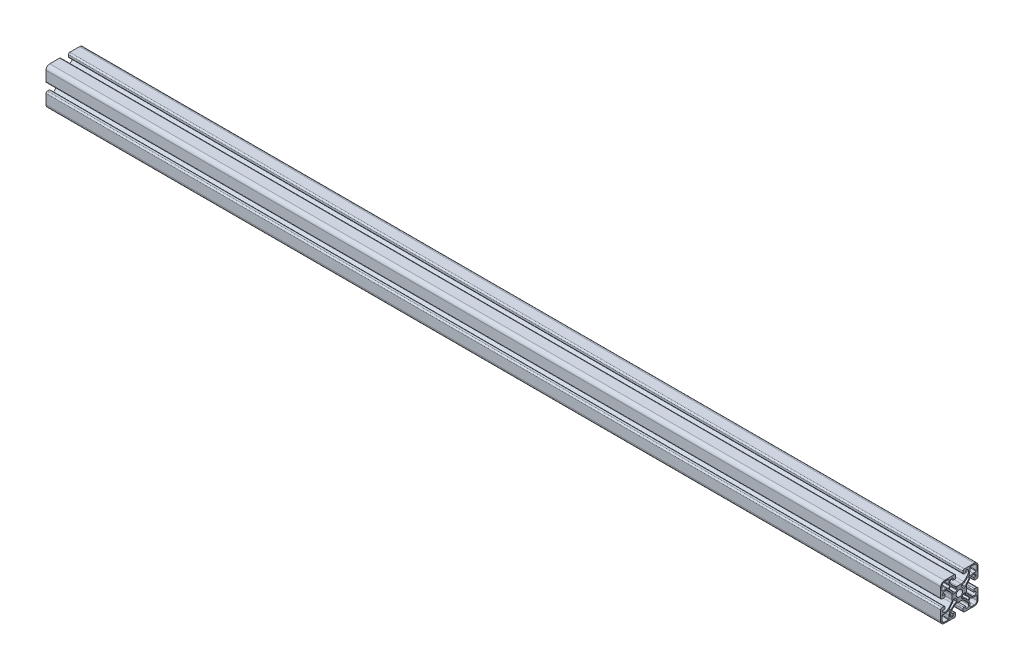
SolidWorks part; units mm, degrees
ref_plane "Front Plane" through (0, 0, 0) normal (1, 0, 0) x (0, 1, 0)
ref_plane "Top Plane" through (0, 0, 0) normal (0, 0, 1) x (0, 1, 0)
ref_plane "Right Plane" through (0, 0, 0) normal (0, 1, 0) x (-1, 0, 0)
sketch "Sketch1" plane through (0, 0, 0) normal (1, 0, 0) x (0, 1, 0)
  line L0 (9.8448, 4.6378) -> (10.0126, 4.8558)
  line L1 (10.4243, 6.082) -> (10.4243, 8.3868)
  line L2 (10.7418, 8.7043) -> (13.4723, 8.7043)
  line L3 (15.2503, 6.9263) -> (15.2503, 4.1958)
  line L4 (14.9328, 3.8783) -> (12.628, 3.8783)
  line L5 (11.4018, 3.4666) -> (11.1838, 3.2989)
  line L6 (10.7635, 3.3243) -> (9.8703, 4.2176)
  line L7 (-4.559, 3.2986) -> (-4.7769, 3.4664)
  line L8 (-6.0032, 3.8781) -> (-8.308, 3.8781)
  line L9 (-8.6255, 4.1956) -> (-8.6255, 6.9261)
  line L10 (-6.8475, 8.7041) -> (-4.117, 8.7041)
  line L11 (-3.7995, 8.3866) -> (-3.7995, 6.0818)
  line L12 (-3.3878, 4.8556) -> (-3.22, 4.6376)
  line L13 (-3.2454, 4.2174) -> (-4.1387, 3.3241)
  line L14 (4.9, -0.3064) -> (4.9, 0.6387)
  line L15 (9.4106, 3.5999) -> (10.1461, 2.8644)
  line L16 (7.1849, -1.6462) -> (6.2397, -1.6462)
  line L17 (0.3853, -1.6462) -> (-0.5599, -1.6462)
  line L18 (-3.521, 2.8644) -> (-2.7855, 3.5999)
  line L19 (1.725, 0.6387) -> (1.725, -0.3064)
  line L20 (-3.2198, -11.1051) -> (-3.3876, -11.3231)
  line L21 (-3.7993, -12.5493) -> (-3.7993, -14.8542)
  line L22 (-4.1168, -15.1717) -> (-6.8473, -15.1717)
  line L23 (-8.6253, -13.3937) -> (-8.6253, -10.6632)
  line L24 (-8.3078, -10.3457) -> (-6.0029, -10.3457)
  line L25 (-4.7767, -9.934) -> (-4.5588, -9.7662)
  line L26 (-4.1385, -9.7916) -> (-3.2452, -10.6849)
  line L27 (11.184, -9.7659) -> (11.402, -9.9337)
  line L28 (12.6282, -10.3454) -> (14.933, -10.3454)
  line L29 (15.2505, -10.6629) -> (15.2505, -13.3934)
  line L30 (13.4725, -15.1714) -> (10.742, -15.1714)
  line L31 (10.4245, -14.8539) -> (10.4245, -12.5491)
  line L32 (10.0128, -11.3229) -> (9.845, -11.1049)
  line L33 (9.8705, -10.6847) -> (10.7638, -9.7914)
  line L34 (1.725, -6.1609) -> (1.725, -7.106)
  line L35 (-2.7855, -10.0672) -> (-3.521, -9.3317)
  line L36 (-0.5599, -4.8212) -> (0.3853, -4.8212)
  line L37 (6.2397, -4.8212) -> (7.1849, -4.8212)
  line L38 (10.1461, -9.3317) -> (9.4106, -10.0672)
  line L39 (4.9, -7.106) -> (4.9, -6.1609)
  line L40 (0.7725, -13.7112) -> (0.7725, -14.9812)
  line L41 (-0.9737, -13.0762) -> (0.1375, -13.0762)
  line L42 (-1.1325, -14.5049) -> (-1.1325, -13.2349)
  line L43 (-1.45, -14.6637) -> (-1.2912, -14.6637)
  line L44 (-3.0375, -12.5811) -> (-3.0375, -13.0762)
  line L45 (4.7051, -8.1549) -> (1.9199, -8.1549)
  line L46 (9.6625, -13.0762) -> (9.6625, -12.5811)
  line L47 (7.9163, -14.6637) -> (8.075, -14.6637)
  line L48 (7.7575, -13.2349) -> (7.7575, -14.5049)
  line L49 (6.4875, -13.0762) -> (7.5988, -13.0762)
  line L50 (5.8525, -14.9812) -> (5.8525, -13.7112)
  line L51 (13.4725, -15.9337) -> (6.805, -15.9337)
  line L52 (16.0125, -6.7262) -> (16.0125, -13.3937)
  line L53 (13.79, -5.7737) -> (15.06, -5.7737)
  line L54 (13.155, -7.5199) -> (13.155, -6.4087)
  line L55 (14.5838, -7.6787) -> (13.3138, -7.6787)
  line L56 (14.7425, -7.9962) -> (14.7425, -7.8374)
  line L57 (12.6599, -9.5837) -> (13.155, -9.5837)
  line L58 (8.2338, -1.8411) -> (8.2338, -4.6262)
  line L59 (13.155, 3.1163) -> (12.6599, 3.1163)
  line L60 (14.7425, 1.3701) -> (14.7425, 1.5288)
  line L61 (13.3138, 1.2113) -> (14.5838, 1.2113)
  line L62 (13.155, -0.0587) -> (13.155, 1.0526)
  line L63 (15.06, -0.6937) -> (13.79, -0.6937)
  line L64 (16.0125, 6.9263) -> (16.0125, 0.2588)
  line L65 (6.805, 9.4663) -> (13.4725, 9.4663)
  line L66 (5.8525, 7.2438) -> (5.8525, 8.5138)
  line L67 (7.5988, 6.6088) -> (6.4875, 6.6088)
  line L68 (7.7575, 8.0376) -> (7.7575, 6.7676)
  line L69 (8.075, 8.1963) -> (7.9163, 8.1963)
  line L70 (9.6625, 6.1138) -> (9.6625, 6.6088)
  line L71 (1.9199, 1.6876) -> (4.7051, 1.6876)
  line L72 (-3.0375, 6.6088) -> (-3.0375, 6.1138)
  line L73 (-1.2912, 8.1963) -> (-1.45, 8.1963)
  line L74 (-1.1325, 6.7676) -> (-1.1325, 8.0376)
  line L75 (0.1375, 6.6088) -> (-0.9737, 6.6088)
  line L76 (0.7725, 8.5138) -> (0.7725, 7.2438)
  line L77 (-6.8475, 9.4663) -> (-0.18, 9.4663)
  line L78 (-9.3875, 0.2588) -> (-9.3875, 6.9263)
  line L79 (-7.165, -0.6937) -> (-8.435, -0.6937)
  line L80 (-6.53, 1.0526) -> (-6.53, -0.0587)
  line L81 (-7.9587, 1.2113) -> (-6.6887, 1.2113)
  line L82 (-8.1175, 1.5288) -> (-8.1175, 1.3701)
  line L83 (-6.0349, 3.1163) -> (-6.53, 3.1163)
  line L84 (-1.6087, -4.6262) -> (-1.6087, -1.8411)
  line L85 (-6.53, -9.5837) -> (-6.0349, -9.5837)
  line L86 (-8.1175, -7.8374) -> (-8.1175, -7.9962)
  line L87 (-6.6887, -7.6787) -> (-7.9587, -7.6787)
  line L88 (-6.53, -6.4087) -> (-6.53, -7.5199)
  line L89 (-8.435, -5.7737) -> (-7.165, -5.7737)
  line L90 (-9.3875, -13.3937) -> (-9.3875, -6.7262)
  line L91 (-0.18, -15.9337) -> (-6.8475, -15.9337)
  arc A0 (9.8448, 4.6378) -> (9.8703, 4.2176) centre (10.0948, 4.4421) ccw
  arc A1 (10.0126, 4.8558) -> (10.4243, 6.082) centre (8.3923, 6.082) ccw
  arc A2 (10.7418, 8.7043) -> (10.4243, 8.3868) centre (10.7418, 8.3868) ccw
  arc A3 (15.2503, 6.9263) -> (13.4723, 8.7043) centre (13.4723, 6.9263) ccw
  arc A4 (14.9328, 3.8783) -> (15.2503, 4.1958) centre (14.9328, 4.1958) ccw
  arc A5 (12.628, 3.8783) -> (11.4018, 3.4666) centre (12.628, 1.8463) ccw
  arc A6 (10.7635, 3.3243) -> (11.1838, 3.2989) centre (10.988, 3.5488) ccw
  arc A7 (-4.559, 3.2986) -> (-4.1387, 3.3241) centre (-4.3632, 3.5486) ccw
  arc A8 (-4.7769, 3.4664) -> (-6.0032, 3.8781) centre (-6.0032, 1.8461) ccw
  arc A9 (-8.6255, 4.1956) -> (-8.308, 3.8781) centre (-8.308, 4.1956) ccw
  arc A10 (-6.8475, 8.7041) -> (-8.6255, 6.9261) centre (-6.8475, 6.9261) ccw
  arc A11 (-3.7995, 8.3866) -> (-4.117, 8.7041) centre (-4.117, 8.3866) ccw
  arc A12 (-3.7995, 6.0818) -> (-3.3878, 4.8556) centre (-1.7675, 6.0818) ccw
  arc A13 (-3.2454, 4.2174) -> (-3.22, 4.6376) centre (-3.47, 4.4419) ccw
  arc A14 (5.9736, -1.5018) -> (6.2397, -1.6462) centre (6.2397, -1.3287) ccw
  arc A15 (5.9736, -1.5018) -> (5.0443, -0.5726) centre (3.3125, -3.2337) ccw
  arc A16 (4.9, -0.3064) -> (5.0443, -0.5726) centre (5.2175, -0.3064) ccw
  arc A17 (5.1763, 0.9535) -> (4.9, 0.6387) centre (5.2175, 0.6387) ccw
  arc A18 (5.1763, 0.9535) -> (6.7288, 1.586) centre (4.7476, 4.2276) ccw
  arc A19 (6.7288, 1.586) -> (8.9531, 3.5911) centre (-3.2534, 14.8956) ccw
  arc A20 (9.4106, 3.5999) -> (8.9531, 3.5911) centre (9.1861, 3.3754) ccw
  arc A21 (10.1373, 2.4069) -> (10.1461, 2.8644) centre (9.9215, 2.6399) ccw
  arc A22 (10.1373, 2.4069) -> (8.1322, 0.1826) centre (21.4418, -9.7996) ccw
  arc A23 (8.1322, 0.1826) -> (7.4997, -1.3699) centre (10.7738, -1.7986) ccw
  arc A24 (7.1849, -1.6462) -> (7.4997, -1.3699) centre (7.1849, -1.3287) ccw
  arc A25 (1.5807, -0.5726) -> (1.725, -0.3064) centre (1.4075, -0.3064) ccw
  arc A26 (1.5807, -0.5726) -> (0.6514, -1.5018) centre (3.3125, -3.2337) ccw
  arc A27 (0.3853, -1.6462) -> (0.6514, -1.5018) centre (0.3853, -1.3287) ccw
  arc A28 (-0.8747, -1.3699) -> (-0.5599, -1.6462) centre (-0.5599, -1.3287) ccw
  arc A29 (-0.8747, -1.3699) -> (-1.5071, 0.1826) centre (-4.1487, -1.7986) ccw
  arc A30 (-1.5071, 0.1826) -> (-3.5122, 2.4069) centre (-14.8167, -9.7996) ccw
  arc A31 (-3.521, 2.8644) -> (-3.5122, 2.4069) centre (-3.2965, 2.6399) ccw
  arc A32 (-2.3281, 3.5911) -> (-2.7855, 3.5999) centre (-2.561, 3.3754) ccw
  arc A33 (-2.3281, 3.5911) -> (-0.1038, 1.586) centre (9.8784, 14.8956) ccw
  arc A34 (-0.1038, 1.586) -> (1.4487, 0.9535) centre (1.8774, 4.2276) ccw
  arc A35 (1.725, 0.6387) -> (1.4487, 0.9535) centre (1.4075, 0.6387) ccw
  arc A36 (-3.2198, -11.1051) -> (-3.2452, -10.6849) centre (-3.4697, -10.9094) ccw
  arc A37 (-3.3876, -11.3231) -> (-3.7993, -12.5493) centre (-1.7673, -12.5493) ccw
  arc A38 (-4.1168, -15.1717) -> (-3.7993, -14.8542) centre (-4.1168, -14.8542) ccw
  arc A39 (-8.6253, -13.3937) -> (-6.8473, -15.1717) centre (-6.8473, -13.3937) ccw
  arc A40 (-8.3078, -10.3457) -> (-8.6253, -10.6632) centre (-8.3078, -10.6632) ccw
  arc A41 (-6.0029, -10.3457) -> (-4.7767, -9.934) centre (-6.0029, -8.3137) ccw
  arc A42 (-4.1385, -9.7916) -> (-4.5588, -9.7662) centre (-4.363, -10.0161) ccw
  arc A43 (11.184, -9.7659) -> (10.7638, -9.7914) centre (10.9883, -10.0159) ccw
  arc A44 (11.402, -9.9337) -> (12.6282, -10.3454) centre (12.6282, -8.3134) ccw
  arc A45 (15.2505, -10.6629) -> (14.933, -10.3454) centre (14.933, -10.6629) ccw
  arc A46 (13.4725, -15.1714) -> (15.2505, -13.3934) centre (13.4725, -13.3934) ccw
  arc A47 (10.4245, -14.8539) -> (10.742, -15.1714) centre (10.742, -14.8539) ccw
  arc A48 (10.4245, -12.5491) -> (10.0128, -11.3229) centre (8.3925, -12.5491) ccw
  arc A49 (9.8705, -10.6847) -> (9.845, -11.1049) centre (10.095, -10.9092) ccw
  arc A50 (0.6514, -4.9655) -> (0.3853, -4.8212) centre (0.3853, -5.1387) ccw
  arc A51 (0.6514, -4.9655) -> (1.5807, -5.8947) centre (3.3125, -3.2337) ccw
  arc A52 (1.725, -6.1609) -> (1.5807, -5.8947) centre (1.4075, -6.1609) ccw
  arc A53 (1.4487, -7.4208) -> (1.725, -7.106) centre (1.4075, -7.106) ccw
  arc A54 (1.4487, -7.4208) -> (-0.1038, -8.0533) centre (1.8774, -10.6949) ccw
  arc A55 (-0.1038, -8.0533) -> (-2.3281, -10.0584) centre (9.8784, -21.3629) ccw
  arc A56 (-2.7855, -10.0672) -> (-2.3281, -10.0584) centre (-2.561, -9.8427) ccw
  arc A57 (-3.5122, -8.8742) -> (-3.521, -9.3317) centre (-3.2965, -9.1072) ccw
  arc A58 (-3.5122, -8.8742) -> (-1.5071, -6.65) centre (-14.8167, 3.3322) ccw
  arc A59 (-1.5071, -6.65) -> (-0.8747, -5.0974) centre (-4.1487, -4.6688) ccw
  arc A60 (-0.5599, -4.8212) -> (-0.8747, -5.0974) centre (-0.5599, -5.1387) ccw
  arc A61 (5.0443, -5.8947) -> (4.9, -6.1609) centre (5.2175, -6.1609) ccw
  arc A62 (5.0443, -5.8947) -> (5.9736, -4.9655) centre (3.3125, -3.2337) ccw
  arc A63 (6.2397, -4.8212) -> (5.9736, -4.9655) centre (6.2397, -5.1387) ccw
  arc A64 (7.4997, -5.0974) -> (7.1849, -4.8212) centre (7.1849, -5.1387) ccw
  arc A65 (7.4997, -5.0974) -> (8.1322, -6.65) centre (10.7738, -4.6688) ccw
  arc A66 (8.1322, -6.65) -> (10.1373, -8.8742) centre (21.4418, 3.3322) ccw
  arc A67 (10.1461, -9.3317) -> (10.1373, -8.8742) centre (9.9215, -9.1072) ccw
  arc A68 (8.9531, -10.0584) -> (9.4106, -10.0672) centre (9.1861, -9.8427) ccw
  arc A69 (8.9531, -10.0584) -> (6.7288, -8.0533) centre (-3.2534, -21.3629) ccw
  arc A70 (6.7288, -8.0533) -> (5.1763, -7.4208) centre (4.7476, -10.6949) ccw
  arc A71 (4.9, -7.106) -> (5.1763, -7.4208) centre (5.2175, -7.106) ccw
  circle A72 centre (3.3125, -3.2337) radius 2.159
  arc A73 (-0.18, -15.9337) -> (0.7725, -14.9812) centre (-0.18, -14.9812) ccw
  arc A74 (0.7725, -13.7112) -> (0.1375, -13.0762) centre (0.1375, -13.7112) ccw
  arc A75 (-0.9737, -13.0762) -> (-1.1325, -13.2349) centre (-0.9737, -13.2349) ccw
  arc A76 (-1.2912, -14.6637) -> (-1.1325, -14.5049) centre (-1.2912, -14.5049) ccw
  arc A77 (-3.0375, -13.0762) -> (-1.45, -14.6637) centre (-1.45, -13.0762) ccw
  arc A78 (-2.7802, -11.8147) -> (-3.0375, -12.5811) centre (-1.7675, -12.5811) ccw
  arc A79 (0.404, -8.6569) -> (-2.7802, -11.8147) centre (9.8784, -21.3947) ccw
  arc A80 (1.9199, -8.1549) -> (0.404, -8.6569) centre (1.9199, -10.6949) ccw
  arc A81 (6.221, -8.6569) -> (4.7051, -8.1549) centre (4.7051, -10.6949) ccw
  arc A82 (9.4052, -11.8147) -> (6.221, -8.6569) centre (-3.2534, -21.3947) ccw
  arc A83 (9.6625, -12.5811) -> (9.4052, -11.8147) centre (8.3925, -12.5811) ccw
  arc A84 (8.075, -14.6637) -> (9.6625, -13.0762) centre (8.075, -13.0762) ccw
  arc A85 (7.7575, -14.5049) -> (7.9163, -14.6637) centre (7.9163, -14.5049) ccw
  arc A86 (7.7575, -13.2349) -> (7.5988, -13.0762) centre (7.5988, -13.2349) ccw
  arc A87 (6.4875, -13.0762) -> (5.8525, -13.7112) centre (6.4875, -13.7112) ccw
  arc A88 (5.8525, -14.9812) -> (6.805, -15.9337) centre (6.805, -14.9812) ccw
  arc A89 (13.4725, -15.9337) -> (16.0125, -13.3937) centre (13.4725, -13.3937) ccw
  arc A90 (16.0125, -6.7262) -> (15.06, -5.7737) centre (15.06, -6.7262) ccw
  arc A91 (13.79, -5.7737) -> (13.155, -6.4087) centre (13.79, -6.4087) ccw
  arc A92 (13.155, -7.5199) -> (13.3138, -7.6787) centre (13.3138, -7.5199) ccw
  arc A93 (14.7425, -7.8374) -> (14.5838, -7.6787) centre (14.5838, -7.8374) ccw
  arc A94 (13.155, -9.5837) -> (14.7425, -7.9962) centre (13.155, -7.9962) ccw
  arc A95 (11.8936, -9.3263) -> (12.6599, -9.5837) centre (12.6599, -8.3137) ccw
  arc A96 (8.7357, -6.1421) -> (11.8936, -9.3263) centre (21.4735, 3.3322) ccw
  arc A97 (8.2338, -4.6262) -> (8.7357, -6.1421) centre (10.7738, -4.6262) ccw
  arc A98 (8.7357, -0.3252) -> (8.2338, -1.8411) centre (10.7738, -1.8411) ccw
  arc A99 (11.8936, 2.859) -> (8.7357, -0.3252) centre (21.4735, -9.7996) ccw
  arc A100 (12.6599, 3.1163) -> (11.8936, 2.859) centre (12.6599, 1.8463) ccw
  arc A101 (14.7425, 1.5288) -> (13.155, 3.1163) centre (13.155, 1.5288) ccw
  arc A102 (14.5838, 1.2113) -> (14.7425, 1.3701) centre (14.5838, 1.3701) ccw
  arc A103 (13.3138, 1.2113) -> (13.155, 1.0526) centre (13.3138, 1.0526) ccw
  arc A104 (13.155, -0.0587) -> (13.79, -0.6937) centre (13.79, -0.0587) ccw
  arc A105 (15.06, -0.6937) -> (16.0125, 0.2588) centre (15.06, 0.2588) ccw
  arc A106 (16.0125, 6.9263) -> (13.4725, 9.4663) centre (13.4725, 6.9263) ccw
  arc A107 (6.805, 9.4663) -> (5.8525, 8.5138) centre (6.805, 8.5138) ccw
  arc A108 (5.8525, 7.2438) -> (6.4875, 6.6088) centre (6.4875, 7.2438) ccw
  arc A109 (7.5988, 6.6088) -> (7.7575, 6.7676) centre (7.5988, 6.7676) ccw
  arc A110 (7.9163, 8.1963) -> (7.7575, 8.0376) centre (7.9163, 8.0376) ccw
  arc A111 (9.6625, 6.6088) -> (8.075, 8.1963) centre (8.075, 6.6088) ccw
  arc A112 (9.4052, 5.3474) -> (9.6625, 6.1138) centre (8.3925, 6.1138) ccw
  arc A113 (6.221, 2.1896) -> (9.4052, 5.3474) centre (-3.2534, 14.9273) ccw
  arc A114 (4.7051, 1.6876) -> (6.221, 2.1896) centre (4.7051, 4.2276) ccw
  arc A115 (0.404, 2.1896) -> (1.9199, 1.6876) centre (1.9199, 4.2276) ccw
  arc A116 (-2.7802, 5.3474) -> (0.404, 2.1896) centre (9.8784, 14.9273) ccw
  arc A117 (-3.0375, 6.1138) -> (-2.7802, 5.3474) centre (-1.7675, 6.1138) ccw
  arc A118 (-1.45, 8.1963) -> (-3.0375, 6.6088) centre (-1.45, 6.6088) ccw
  arc A119 (-1.1325, 8.0376) -> (-1.2912, 8.1963) centre (-1.2912, 8.0376) ccw
  arc A120 (-1.1325, 6.7676) -> (-0.9737, 6.6088) centre (-0.9737, 6.7676) ccw
  arc A121 (0.1375, 6.6088) -> (0.7725, 7.2438) centre (0.1375, 7.2438) ccw
  arc A122 (0.7725, 8.5138) -> (-0.18, 9.4663) centre (-0.18, 8.5138) ccw
  arc A123 (-6.8475, 9.4663) -> (-9.3875, 6.9263) centre (-6.8475, 6.9263) ccw
  arc A124 (-9.3875, 0.2588) -> (-8.435, -0.6937) centre (-8.435, 0.2588) ccw
  arc A125 (-7.165, -0.6937) -> (-6.53, -0.0587) centre (-7.165, -0.0587) ccw
  arc A126 (-6.53, 1.0526) -> (-6.6887, 1.2113) centre (-6.6887, 1.0526) ccw
  arc A127 (-8.1175, 1.3701) -> (-7.9587, 1.2113) centre (-7.9587, 1.3701) ccw
  arc A128 (-6.53, 3.1163) -> (-8.1175, 1.5288) centre (-6.53, 1.5288) ccw
  arc A129 (-5.2685, 2.859) -> (-6.0349, 3.1163) centre (-6.0349, 1.8463) ccw
  arc A130 (-2.1107, -0.3252) -> (-5.2685, 2.859) centre (-14.8485, -9.7996) ccw
  arc A131 (-1.6087, -1.8411) -> (-2.1107, -0.3252) centre (-4.1487, -1.8411) ccw
  arc A132 (-2.1107, -6.1421) -> (-1.6087, -4.6262) centre (-4.1487, -4.6262) ccw
  arc A133 (-5.2685, -9.3263) -> (-2.1107, -6.1421) centre (-14.8485, 3.3322) ccw
  arc A134 (-6.0349, -9.5837) -> (-5.2685, -9.3263) centre (-6.0349, -8.3137) ccw
  arc A135 (-8.1175, -7.9962) -> (-6.53, -9.5837) centre (-6.53, -7.9962) ccw
  arc A136 (-7.9587, -7.6787) -> (-8.1175, -7.8374) centre (-7.9587, -7.8374) ccw
  arc A137 (-6.6887, -7.6787) -> (-6.53, -7.5199) centre (-6.6887, -7.5199) ccw
  arc A138 (-6.53, -6.4087) -> (-7.165, -5.7737) centre (-7.165, -6.4087) ccw
  arc A139 (-8.435, -5.7737) -> (-9.3875, -6.7262) centre (-8.435, -6.7262) ccw
  arc A140 (-9.3875, -13.3937) -> (-6.8475, -15.9337) centre (-6.8475, -13.3937) ccw
  dimension "D1" = 25.4
extrude "Boss-Extrude1" add sketch "Sketch1" along normal blind 609.6
